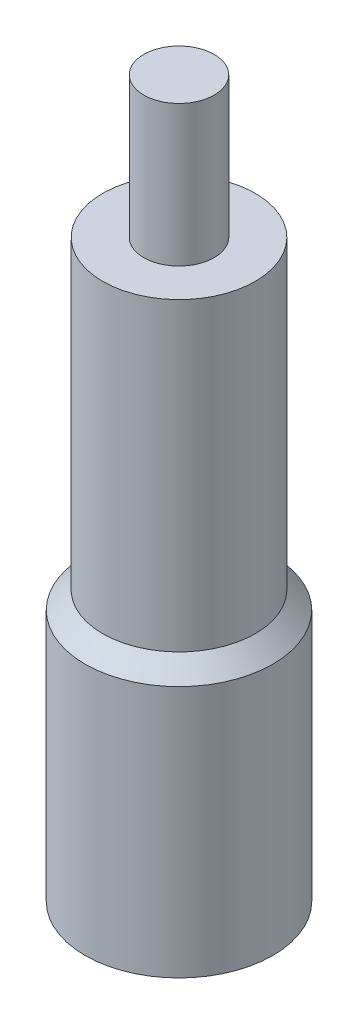
SolidWorks part; units mm, degrees
material "6061 合金"
ref_plane "前视基准面" through (0, 0, 0) normal (0, 0, 1) x (1, 0, 0)
ref_plane "上视基准面" through (0, 0, 0) normal (0, 1, 0) x (1, 0, 0)
ref_plane "右视基准面" through (0, 0, 0) normal (1, 0, 0) x (0, 0, -1)
sketch "草图1" plane through (0, 0, 0) normal (0, 1, 0) x (1, 0, 0)
  circle A0 centre (0, 0) radius 4
  dimension "D1" = 8
extrude "凸台-拉伸1" add sketch "草图1" along normal blind 24.5
sketch "草图2" plane through (0, 24.5, 0) normal (0, 1, 0) x (1, 0, 0)
  circle A0 centre (0, 0) radius 1.5
  dimension "D1" = 3
extrude "凸台-拉伸2" add sketch "草图2" along normal blind 6
cosmetic thread "装饰螺纹线1" parameters "D2"=2.459
hole_wizard "M5 螺纹孔1" positions "草图3" profile "草图4" tap size "M5" standard "GB"
sketch "草图3" plane through (0, 0, 0) normal (0, -1, 0) x (-1, 0, 0)
  point P0 (0, 0)
sketch "草图4" plane through (0, 0, 0) normal (1, 0, 0) x (0, 0, -1)
  line L0 (0, 0) -> (0, 11.2618)
  line L1 (0, 11.2618) -> (2.1, 10)
  line L2 (2.1, 10) -> (2.1, 0)
  line L5 (2.1, 0) -> (0, 0)
  line L10 (0, 11.2618) -> (-2.1, 10) construction
  line L11 (0, -6.35) -> (0, 107.95) construction
  dimension "螺纹孔钻头直径" = 4.2
  dimension "螺纹孔钻头深度" = 10
  dimension "导头角度" = 118
cosmetic thread "孔螺蚊线1" parameters "D1"=9, "D2"=5
sketch "草图5" plane through (0, 24.5, 0) normal (0, 1, 0) x (1, 0, 0)
  circle A0 centre (0, 0) radius 3.25
  dimension "D1" = 6.5
extrude "切除-拉伸1" cut sketch "草图5" against normal blind 13 flip side to cut
chamfer "倒角1" distance 0.75 angle 45 1 edges at (0, 11.5, 4)
